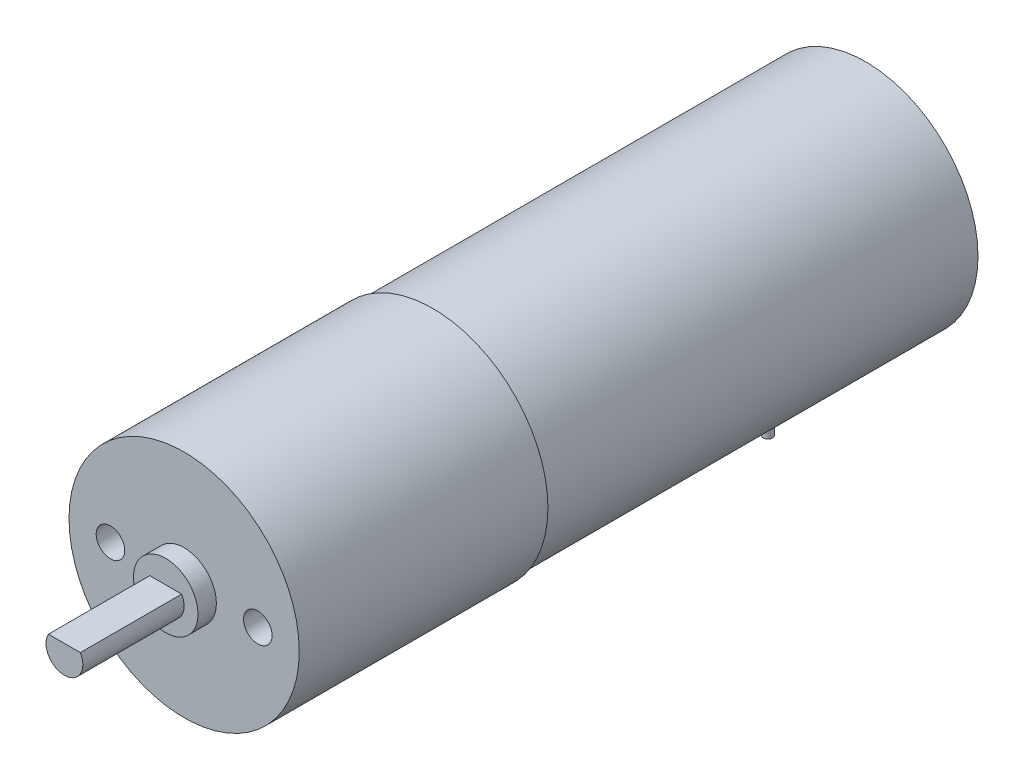
SolidWorks part; units mm, degrees
ref_plane "Front Plane" through (0, 0, 0) normal (0, 0, 1) x (1, 0, 0)
ref_plane "Top Plane" through (0, 0, 0) normal (0, 1, 0) x (1, 0, 0)
ref_plane "Right Plane" through (0, 0, 0) normal (1, 0, 0) x (0, 0, -1)
sketch "Sketch1" plane through (0, 0, 0) normal (0, 0, 1) x (1, 0, 0)
  circle A0 centre (0, 0) radius 12.2
  dimension "D1" = 24.4
extrude "Boss-Extrude1" add sketch "Sketch1" along normal blind 47
sketch "Sketch2" plane through (0, 0, 47) normal (0, 0, 1) x (1, 0, 0)
  circle A0 centre (0, 0) radius 12.5
  dimension "D1" = 25
extrude "Boss-Extrude2" add sketch "Sketch2" along normal blind 27
sketch "Sketch3" plane through (0, 0, 74) normal (0, 0, 1) x (1, 0, 0)
  circle A0 centre (0, 0) radius 3.5
  dimension "D1" = 7
extrude "Boss-Extrude3" add sketch "Sketch3" along normal blind 2
sketch "Sketch4" plane through (0, 0, 76) normal (0, 0, 1) x (1, 0, 0)
  line L0 (-1.7321, 1) -> (1.7321, 1)
  arc A0 (-1.7321, 1) -> (1.7321, 1) centre (0, 0) ccw
  dimension "D1" = 4
  dimension "D2" = 1
extrude "Boss-Extrude4" add sketch "Sketch4" along normal blind 11
sketch "Sketch6" plane through (0, 0, 0) normal (0, 1, 0) x (1, 0, 0)
  line L0 (12.2, 0) -> (-12.2, 0) construction
  line L1 (-6.5, -15) -> (6.5, -15)
  line L2 (-6.5, -15) -> (-6.5, -10)
  line L3 (-6.5, -10) -> (6.5, -10)
  line L4 (6.5, -15) -> (6.5, -10)
  line L5 (-6.5, -15) -> (6.5, -10) construction
  line L6 (-6.5, -10) -> (6.5, -15) construction
  point P4 (0, -12.5)
  dimension "D1" = 15
  dimension "D2" = 5
  dimension "D3" = 13
extrude "Cut-Extrude1" cut sketch "Sketch6" against normal blind 15
sketch "Sketch7" plane through (0, 0, 15) normal (0, 0, -1) x (-1, 0, 0)
  line L1 (-4.0911, -10.5) -> (3.9089, -10.5)
  line L2 (-4.0911, -10.5) -> (-4.0911, -7.5)
  line L3 (-4.0911, -7.5) -> (3.9089, -7.5)
  line L4 (3.9089, -10.5) -> (3.9089, -7.5)
  line L5 (-4.0911, -10.5) -> (3.9089, -7.5) construction
  line L6 (-4.0911, -7.5) -> (3.9089, -10.5) construction
  arc A0 (-6.5, -10.3242) -> (6.5, -10.3242) centre (0, 0) ccw construction
  arc A1 (-6.5, -10.3242) -> (6.5, -10.3242) centre (0, 0) ccw construction
  point P3 (-0.0911, -9)
  dimension "D1" = 3
  dimension "D2" = 8
  dimension "D3" = 9
extrude "Boss-Extrude6" add sketch "Sketch7" along normal blind 2.5
sketch "Sketch8" plane through (0, -10.5, 0) normal (0, -1, 0) x (1, 0, 0)
  line L0 (-3.9089, 12.5) -> (-3.9089, 15) construction
  circle A0 centre (-2.8633, 13.75) radius 0.5
  circle A1 centre (-1.6633, 13.75) radius 0.5
  circle A2 centre (-0.4633, 13.75) radius 0.5
  circle A3 centre (0.7367, 13.75) radius 0.5
  circle A4 centre (1.9367, 13.75) radius 0.5
  circle A5 centre (3.1367, 13.75) radius 0.5
  point P16 (-3.9089, 13.75)
  dimension "D2" = 1
  dimension "D1" = 6
extrude "Boss-Extrude7" add sketch "Sketch8" along normal blind 4
draft "Draft1" type of draft neutral plane draft angle 5 faces to draft 2 face at (4.0911, -9, 13.75) face at (-3.9089, -9, 13.75) neutral plane through (0, 0, 12.5) neutral plane normal (0, 0, -1) parameters "D1"=5
sketch "Sketch9" plane through (0, 0, 74) normal (0, 0, 1) x (1, 0, 0)
  line L0 (0, -14.85) -> (0, 14.85) construction
  line L1 (-3.5, 0) -> (-12.5, 0) construction
  circle A0 centre (-8, 0) radius 1.55
  circle A1 centre (8, 0) radius 1.55
  circle A2 centre (0, 0) radius 3.5 construction
  circle A3 centre (0, 0) radius 12.5 construction
  circle A4 centre (0, 0) radius 12.5 construction
  circle A5 centre (0, 0) radius 3.5 construction
  point P15 (-8, 0)
  dimension "D1" = 3.1
extrude "Cut-Extrude2" cut sketch "Sketch9" against normal blind 4
